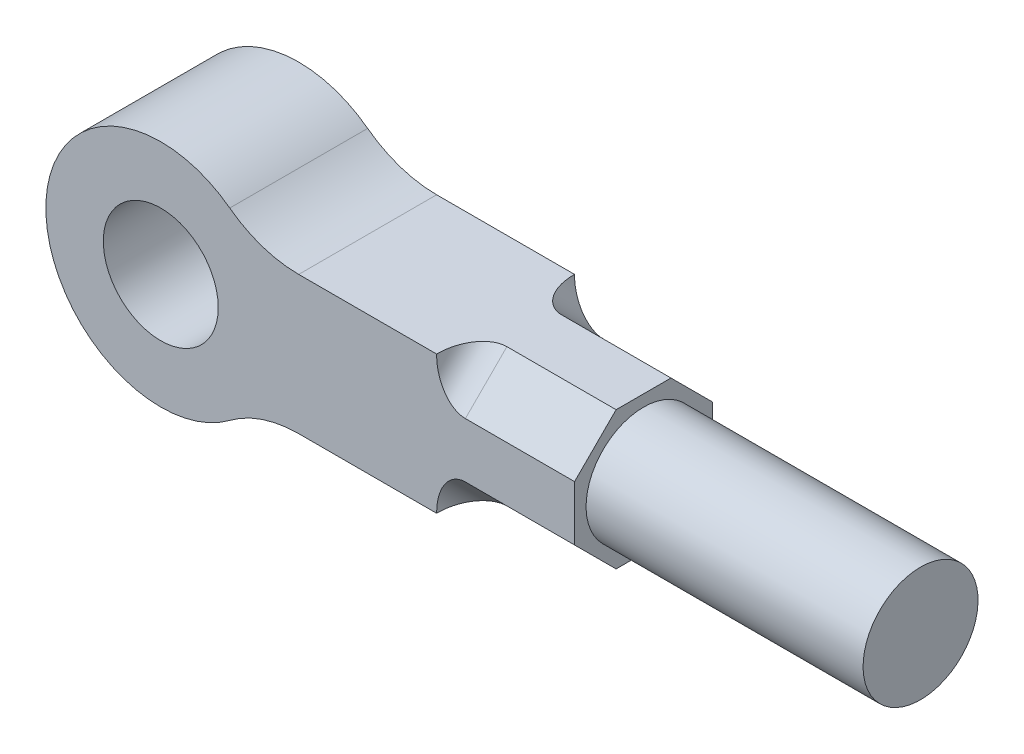
SolidWorks part; units mm, degrees
ref_plane "Front Plane" through (0, 0, 0) normal (0, 0, 1) x (1, 0, 0)
ref_plane "Top Plane" through (0, 0, 0) normal (0, 1, 0) x (1, 0, 0)
ref_plane "Right Plane" through (0, 0, 0) normal (1, 0, 0) x (0, 0, -1)
sketch "Sketch1" plane through (0, 0, 0) normal (0, 0, 1) x (1, 0, 0)
  line L1 (60, 30) -> (180, 30)
  line L3 (60, -30) -> (180, -30)
  line L4 (180, 30) -> (180, -30)
  arc A0 (30, 40) -> (30, -40) centre (0, 0) ccw
  circle A1 centre (0, 0) radius 25
  arc A2 (30, -40) -> (60, -30) centre (60, -80) cw
  arc A3 (60, 30) -> (30, 40) centre (60, 80) cw
  point P8 (57.6017, 0.0908)
  point P9 (0, 0)
  point P10 (0, 0)
  point P12 (40, -30)
  point P15 (40, 30)
  dimension "D1" = 100
  dimension "D2" = 50
  dimension "D9" = 50
  dimension "D3" = 140
  dimension "D4" = 140
  dimension "D5" = 60
  dimension "D6" = 60
  dimension "D7" = 30
  dimension "D8" = 30
extrude "Boss-Extrude1" add sketch "Sketch1" along normal mid plane 60
sketch "Sketch2" plane through (180, 0, 0) normal (1, 0, 0) x (0, 0, -1)
  line L1 (30, -30) -> (30, 30) construction
  line L2 (-30, 30) -> (30, 30) construction
  line L3 (30, 11.94) -> (30, 30)
  line L4 (11.94, 30) -> (30, 30)
  line L5 (11.94, 30) -> (30, 11.94)
  line L6 (11.94, -30) -> (30, -30)
  line L7 (30, -11.94) -> (11.94, -30)
  line L8 (30, -11.94) -> (30, -30)
  line L9 (-30, -11.94) -> (-30, -30)
  line L10 (-11.94, -30) -> (-30, -11.94)
  line L11 (-11.94, -30) -> (-30, -30)
  line L12 (-11.94, 30) -> (-30, 30)
  line L13 (-30, 11.94) -> (-11.94, 30)
  line L14 (-30, 11.94) -> (-30, 30)
  circle A0 centre (0, 0) radius 25
  line M4 (30, -30) -> (30, 30)
  line M5 (30, 30) -> (-30, 30)
  line M6 (-30, 30) -> (-30, -30)
  line M7 (-30, -30) -> (30, -30)
  dimension "D1" = 50
  dimension "D2" = 30
  dimension "D3" = 18.06
  dimension "D4" = 18.06
  dimension "D5" = 4
extrude "Cut-Extrude1" cut sketch "Sketch2" against normal blind 60 contours L13 M6 M5 | L10 M7 M6 | L5 M5 M4 | L7 M4 M7 region at (180, 23.98, -23.98) region at (180, -23.98, -23.98) region at (180, 23.98, 23.98) region at (180, -23.98, 23.98)
extrude "Boss-Extrude2" add sketch "Sketch2<3>" along normal blind 120.5 contours A0 region at (180, 0, 0)
sketch "Sketch2<3>" plane through (180, 0, 0) normal (1, 0, 0) x (0, 0, -1) same geometry as "Sketch2"
fillet "Fillet1" radius 12.5 4 edges at (120, -20.97, -20.97) (120, 20.97, -20.97) (120, -20.97, 20.97) (120, 20.97, 20.97)
